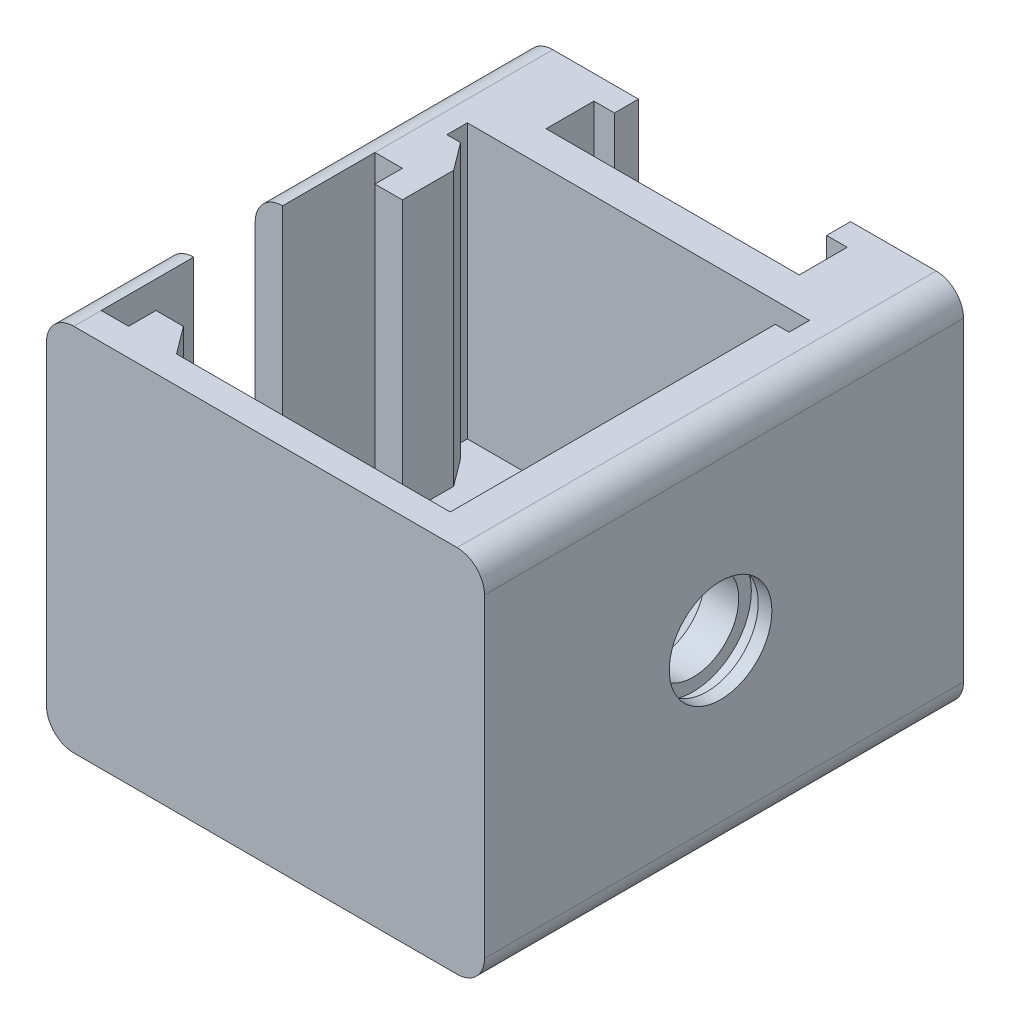
SolidWorks part; units mm, degrees
material "UNOBTANIUM"
ref_plane "Top Plane" through (0, 0, 0) normal (0, 0, 1) x (1, 0, 0)
ref_plane "Right Plane" through (0, 0, 0) normal (0, 1, 0) x (1, 0, 0)
ref_plane "Front Plane" through (0, 0, 0) normal (1, 0, 0) x (0, 0, -1)
ref_axis "x-axis" through (-17.6, 0, 0) along (1, 0, 0)
ref_axis "y-axis" through (0, -14.85, 0) along (0, 1, 0)
ref_axis "z-axis" through (0, 0, 36.75) along (0, 0, -1)
sketch "Sketch1" plane through (0, 0, 0) normal (0, 0, 1) x (1, 0, 0)
  line L1 (-16, 13.5) -> (16, 13.5)
  line L2 (-16, 13.5) -> (-16, -13.5)
  line L3 (-16, -13.5) -> (16, -13.5)
  line L4 (16, 13.5) -> (16, -13.5)
  line L5 (-16, 13.5) -> (16, -13.5) construction
  line L6 (-16, -13.5) -> (16, 13.5) construction
  point P0 (0, 0)
  dimension "D1" = 32
  dimension "D2" = 27
extrude "Boss-Extrude1" add sketch "Sketch1" along normal blind 35
fillet "Fillet1" radius 2 4 edges at (16, -13.5, 17.5) (16, 13.5, 17.5) (-16, -13.5, 17.5) (-16, 13.5, 17.5)
sketch "Sketch2" plane through (0, -13.5, 0) normal (0, -1, 0) x (1, 0, 0)
  line L0 (-7.75, 0) -> (-7.75, 1.75)
  line L1 (-14, 0) -> (14, 0) construction
  line L2 (-7.75, 1.75) -> (-9.25, 1.75)
  line L3 (-9.25, 1.75) -> (-9.25, 5.25)
  line L4 (-9.25, 5.25) -> (9.25, 5.25)
  line L5 (9.25, 5.25) -> (9.25, 1.75)
  line L6 (9.25, 1.75) -> (7.75, 1.75)
  line L7 (7.75, 1.75) -> (7.75, 0)
  line L9 (-7.75, 0) -> (7.75, 0)
  point P4 (0, 0)
  dimension "D1" = 15.5
  dimension "D2" = 1.75
  dimension "D3" = 3.5
  dimension "D4" = 18.5
extrude "Cut-Extrude1" cut sketch "Sketch2" against normal through all both and the other way through all
sketch "Sketch3" plane through (0, -13.5, 0) normal (0, -1, 0) x (1, 0, 0)
  line L0 (-7.75, 0) -> (-7.75, 1.75)
  line L1 (-7.75, 1.75) -> (-9.25, 1.75)
  line L2 (-9.25, 1.75) -> (-9.25, 5.25)
  line L3 (-9.25, 5.25) -> (9.25, 5.25)
  line L4 (9.25, 5.25) -> (9.25, 1.75)
  line L5 (9.25, 1.75) -> (7.75, 1.75)
  line L6 (7.75, 1.75) -> (7.75, 0)
  line L7 (7.75, 0) -> (-7.75, 0)
extrude "Boss-Extrude2" add sketch "Sketch3" against normal blind 7
sketch "Sketch4" plane through (0, 0, 1.75) normal (0, 0, -1) x (-1, 0, 0)
  line L1 (-7.75, 6.5) -> (-7.75, 5.5)
  line L2 (-7.75, 13.5) -> (-7.75, -6.5) construction
  arc A0 (-7.75, 6.5) -> (-7.75, 5.5) centre (-8.125, 6) cw
  dimension "D1" = 0.625
  dimension "D2" = 0.25
  dimension "D3" = 7
extrude "Boss-Extrude3" add sketch "Sketch4" along normal up to surface (1.75 mm away) up to face at (0, 1.1667, 0)
mirror "Mirror1" about plane through (0, 0, 0) normal (1, 0, 0) of "Boss-Extrude3"
sketch "Sketch5" plane through (0, 0, 0) normal (0, 0, -1) x (-1, 0, 0)
  line L0 (7.75, -6.5) -> (-7.75, -6.5) construction
  line L1 (-1, -6.5) -> (1, -6.5)
  line L2 (-1, -6.5) -> (-1, -13.5)
  line L3 (-1, -13.5) -> (1, -13.5)
  line L4 (1, -6.5) -> (1, -13.5)
  line L5 (14, -13.5) -> (-14, -13.5) construction
  point P8 (0, -6.5)
  dimension "D1" = 2
extrude "Cut-Extrude2" cut sketch "Sketch5" against normal offset from surface (33 mm away) 2 up to face at (0, 0, 35)
sketch "Sketch6" plane through (0, 13.5, 0) normal (0, 1, 0) x (1, 0, 0)
  line L0 (-12.5, -7.75) -> (-12.5, -9.25)
  line L1 (-12.5, -9.25) -> (-11.5, -9.25)
  line L2 (-11.5, -9.25) -> (-11.5, -33)
  line L3 (-11.5, -33) -> (11.5, -33)
  line L4 (11.5, -33) -> (11.5, -9.25)
  line L5 (11.5, -9.25) -> (12.5, -9.25)
  line L6 (12.5, -9.25) -> (12.5, -7.75)
  line L7 (12.5, -7.75) -> (-12.5, -7.75)
  line L8 (9.25, -5.25) -> (-9.25, -5.25) construction
  line L9 (0, -7.75) -> (0, -5.25) construction
  line L10 (14, -35) -> (-14, -35) construction
  dimension "D1" = 2.5
  dimension "D2" = 1.5
  dimension "D3" = 1
  dimension "D4" = 25
  dimension "D5" = 2
extrude "Cut-Extrude3" cut sketch "Sketch6" against normal up to surface (20 mm away) up to face at (6, -6.5, 2.3333)
sketch "Sketch7" plane through (0, -13.5, 0) normal (0, -1, 0) x (1, 0, 0)
  line L0 (1, 0) -> (14, 0) construction
  line L1 (1, 0) -> (-1, 0)
  line L2 (1, 0) -> (1, 33)
  line L3 (1, 33) -> (-1, 33)
  line L4 (-1, 0) -> (-1, 33)
  line L5 (1, 33) -> (1, 0) construction
extrude "Boss-Extrude4" add sketch "Sketch7" against normal blind 0.25
fillet "Fillet2" radius 6 1 edges at (0, -13.25, 33)
ref_axis "Axis1" through (63.07, 0, 17.75) along (-1, 0, 0)
ref_plane "Plane1" through (0, 0, 17.75) normal (0, 0, -1) x (-1, 0, 0)
sketch "Sketch9" plane through (0, 0, 17.75) normal (0, 0, -1) x (-1, 0, 0)
  line L0 (-15, 4.25) -> (-14, 4.25)
  line L1 (-16, -11.5) -> (-16, 11.5) construction
  line L2 (-14, 4.25) -> (-14, 3.325)
  line L3 (-14, 3.325) -> (-11.5, 3.325)
  line L4 (-11.5, 3.325) -> (-11.5, 0)
  line L5 (-63.07, 0) -> (46.93, 0) construction
  line L6 (-11.5, 0) -> (-16, 0)
  line L8 (-16, 0) -> (-0.664, 0) construction
  line L9 (-11.5, -6.5) -> (-11.5, 13.5) construction
  line L10 (-15, 4.25) -> (-15, 3.75)
  line L11 (-15, 3.75) -> (-16, 3.75)
  line L12 (-16, 3.75) -> (-16, 0)
  dimension "D1" = 6.65
  dimension "D2" = 8.5
  dimension "D3" = 1
  dimension "D4" = 1
  dimension "D5" = 7.5
revolve "Cut-Revolve1" cut sketch "Sketch9" angle 360 about L8
sketch "Sketch10" plane through (0, 13.5, 0) normal (0, 1, 0) x (1, 0, 0)
  line L0 (11.5, -31) -> (13.5, -31)
  line L1 (11.5, -9.25) -> (11.5, -33) construction
  line L2 (13.5, -31) -> (13.5, -33)
  line L3 (13.5, -33) -> (11.5, -33)
  line L4 (11.5, -33) -> (11.5, -31)
  dimension "D1" = 2
  dimension "D2" = 2
extrude "Cut-Extrude4" [suppressed] cut sketch "Sketch10" against normal up to surface (20 mm away)
mirror "Mirror2" [suppressed] about plane through (0, 0, 0) normal (1, 0, 0)
sketch "Sketch11" plane through (-16, 0, 44) normal (1, 0, 0) x (0, 0, -1)
  line L0 (21, 23) -> (21, 0) construction
  line L4 (24.25, 23) -> (24.25, 0)
  line L5 (17.75, 23) -> (17.75, 0)
  line L6 (9, 11.5) -> (44, 11.5) construction
  line L7 (21, 0) -> (44, 0) construction
  line L8 (9, 11.5) -> (9, -11.5) construction
  arc A2 (24.25, 23) -> (17.75, 23) centre (21, 23) ccw
  arc A3 (17.75, 0) -> (24.25, 0) centre (21, 0) ccw
  point P2 (21, 11.5)
  dimension "D1" = 6.5
  dimension "D2" = 12
extrude "Cut-Extrude5" cut sketch "Sketch11" along normal up to surface (4.5 mm away) up to face at (-11.5, 3.5, 21.125)
sketch "Sketch14" plane through (0, 13.5, 0) normal (0, 1, 0) x (1, 0, 0)
  line L0 (-11.5, -9.25) -> (-11.5, -19.75) construction
  line L1 (-11.5, -13) -> (-14, -13)
  line L2 (-11.5, -13) -> (-11.5, -33)
  line L3 (-11.5, -33) -> (-14, -33)
  line L4 (-14, -13) -> (-14, -33)
  line L5 (-16, -35) -> (-16, -26.25) construction
  line L6 (-11.5, -26.25) -> (-11.5, -19.75) construction
  point P12 (-11.5, -23)
  dimension "D1" = 2
extrude "Cut-Extrude6" cut sketch "Sketch14" against normal up to surface (20 mm away) up to face at (-8.3333, -6.5, 16.6667)
sketch "Sketch16" plane through (0, 13.5, 0) normal (0, 1, 0) x (1, 0, 0)
  line L1 (-12, -11.25) -> (-10, -11.25)
  line L2 (-12, -11.25) -> (-12, -15)
  line L3 (-12, -15) -> (-10, -15)
  line L4 (-10, -11.25) -> (-10, -15)
  line L5 (-14, -33) -> (-14, -13) construction
  line L6 (-12, -33) -> (-12, -31)
  line L7 (-14, -33) -> (11.5, -33) construction
  line L8 (-12, -31) -> (-10, -31)
  line L9 (-10, -31) -> (-10, -33)
  line L10 (-10, -33) -> (-12, -33)
  line L11 (-12.5, -9.25) -> (-11.5, -9.25) construction
  line L13 (-11.5, -13) -> (-14, -13) construction
  line L14 (-14, -13) -> (-14, -19.75) construction
  dimension "D1" = 4
  dimension "D2" = 2
  dimension "D3" = 2
  dimension "D4" = 2
  dimension "D5" = 2
extrude "Boss-Extrude5" add sketch "Sketch16" against normal up to surface (20 mm away) up to face at (-9.75, -6.5, 15.75)
sketch "Sketch20" plane through (0, 13.5, 0) normal (0, 1, 0) x (1, 0, 0)
  line L0 (-11.5, -9.25) -> (-10, -11.25)
  line L1 (-10, -11.25) -> (-11.5, -11.25)
  line L2 (-11.5, -11.25) -> (-11.5, -9.25)
  line L3 (-10, -31) -> (-8.5, -33)
  line L4 (-1, -33) -> (-10, -33) construction
  line L5 (-8.5, -33) -> (-10, -33)
  line L6 (-10, -33) -> (-10, -31)
extrude "Boss-Extrude6" add sketch "Sketch20" against normal up to surface (20 mm away) up to face at (-10.375, -6.5, 19.1562)
